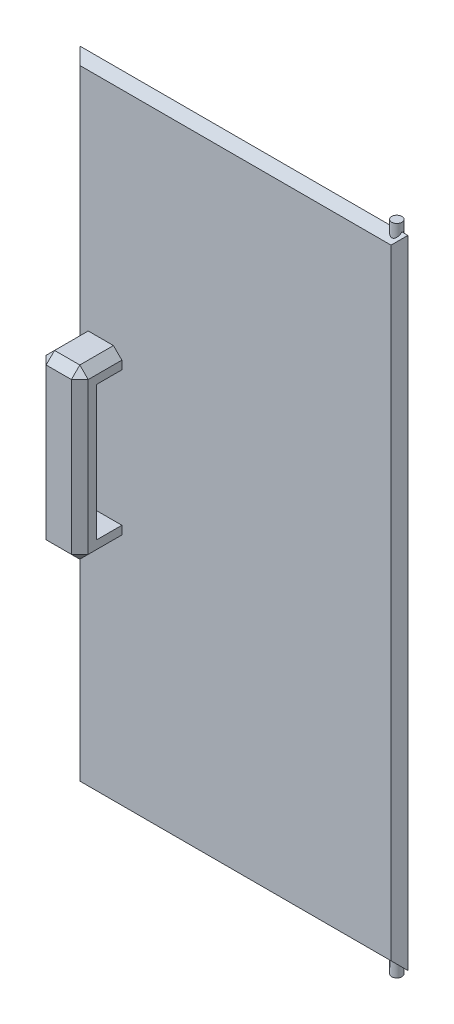
SolidWorks part; units mm, degrees
ref_plane "Front Plane" through (0, 0, 0) normal (0, 0, 1) x (1, 0, 0)
ref_plane "Top Plane" through (0, 0, 0) normal (0, 1, 0) x (1, 0, 0)
ref_plane "Right Plane" through (0, 0, 0) normal (1, 0, 0) x (0, 0, -1)
sketch "Sketch1" plane through (0, 0, 0) normal (0, 0, 1) x (1, 0, 0)
  line L0 (-47.1094, 19.5562) -> (342.8906, 19.5562)
  line L1 (342.8906, 19.5562) -> (342.8906, -737.2438)
  line L2 (342.8906, -737.2438) -> (-47.1094, -737.2438)
  line L3 (-47.1094, -737.2438) -> (-47.1094, 19.5562)
extrude "Boss-Extrude1" add sketch "Sketch1" along normal blind 20
sketch "Sketch2" plane through (0, 19.5562, 0) normal (0, 1, 0) x (1, 0, 0)
  circle A0 centre (329.7783, -10) radius 6.05
extrude "Boss-Extrude2" add sketch "Sketch2" along normal blind 10
sketch "Sketch3" plane through (0, -737.2438, 0) normal (0, -1, 0) x (1, 0, 0)
  circle A0 centre (329.7783, 10) radius 6.05
  point P2 (329.7783, 10)
extrude "Boss-Extrude3" add sketch "Sketch3" along normal blind 10
chamfer "Chamfer1" distance 10 angle 45 8 edges at (147.8906, -737.2438, 0) (-47.1094, -358.8438, 0) (147.8906, 19.5562, 0) (342.8906, -358.8438, 0) (147.8906, -737.2438, 20) (-47.1094, -358.8438, 20) (147.8906, 19.5562, 20) (342.8906, -358.8438, 20)
sketch "Sketch4" plane through (0, 0, 20) normal (0, 0, 1) x (1, 0, 0)
  line L0 (-37.1094, 9.5562) -> (-37.1094, -358.8438)
  line L1 (-37.1094, 9.5562) -> (-37.1094, -727.2438) construction
  line L3 (12.8906, -358.8438) -> (12.8906, -258.8438)
  line L4 (12.8906, -258.8438) -> (-37.1094, -258.8438)
  line L5 (-37.1094, -258.8438) -> (-37.1094, -458.8438)
  line L6 (-37.1094, -458.8438) -> (12.8906, -458.8438)
  line L7 (12.8906, -458.8438) -> (12.8906, -358.8438)
extrude "Boss-Extrude4" add sketch "Sketch4" along normal blind 50 contours L6 L7 L3 L4 L0 region at (-12.1094, -358.8438, 20)
sketch "Sketch5" plane through (-37.1094, 0, 0) normal (-1, 0, 0) x (0, 0, 1)
  line L0 (20, -258.8438) -> (20, -278.8438)
  line L1 (20, -258.8438) -> (20, -458.8438) construction
  line L2 (20, -278.8438) -> (50, -278.8438)
  line L3 (50, -278.8438) -> (50, -438.8438)
  line L4 (50, -438.8438) -> (20, -438.8438)
  line L5 (20, -438.8438) -> (20, -278.8438)
  line M1 (20, -258.8438) -> (20, -458.8438)
extrude "Cut-Extrude1" cut sketch "Sketch5" against normal blind 131 contours L4 L3 L2 M1 region at (-37.1094, -358.8438, 35)
chamfer "Chamfer2" distance 10 angle 45 8 edges at (-37.1094, -358.8438, 70) (-37.1094, -458.8438, 45) (-12.1094, -458.8438, 70) (12.8906, -458.8438, 45) (12.8906, -358.8438, 70) (12.8906, -258.8438, 45) (-12.1094, -258.8438, 70) (-37.1094, -258.8438, 45)
